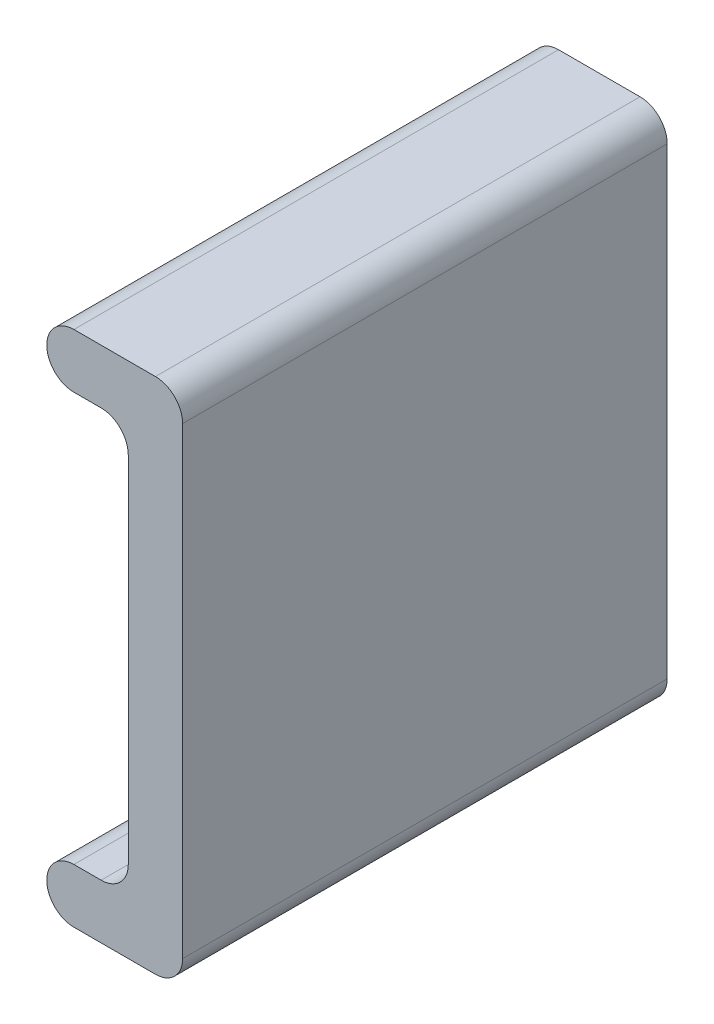
SolidWorks part; units mm, degrees
material "ABS"
ref_plane "X-Y Datum" through (0, 0, 0) normal (0, 0, 1) x (1, 0, 0)
ref_plane "X-Z Datum" through (0, 0, 0) normal (0, 1, 0) x (1, 0, 0)
ref_plane "Y-Z Datum" through (0, 0, 0) normal (1, 0, 0) x (0, 0, -1)
sketch "Sketch1" plane through (0, 0, 0) normal (0, 0, 1) x (1, 0, 0)
  line L1 (0, 0) -> (15, 0)
  line L2 (0, 0) -> (0, 6)
  line L3 (0, 6) -> (9, 6)
  line L4 (15, 0) -> (15, 6.15)
  line L6 (15, 6.15) -> (15, 57.15)
  line L8 (9, 6) -> (9, 51.15)
  line L9 (15, 57.15) -> (0, 57.15)
  line L10 (15, 57.15) -> (15, 53.7541)
  line L11 (9, 51.15) -> (0, 51.15)
  line L12 (0, 57.15) -> (0, 51.15)
  point P12 (0, 54.15)
  dimension "D1" = 15
  dimension "D2" = 57.15
  dimension "D3" = 6
  dimension "D4" = 6
  dimension "D5" = 6
  dimension "D6" = 15
extrude "Boss-Extrude1" add sketch "Sketch1" along normal blind 53.5 contours L9 L12 L11 L8 L3 L2 L1 L4 L6 region at (10.2036, 28.575, 0)
fillet "Fillet4" radius 3 8 edges at (0, 6, 26.75) (9, 6, 26.75) (15, 0, 26.75) (0, 0, 26.75) (15, 57.15, 26.75) (0, 57.15, 26.75) (9, 51.15, 26.75) (0, 51.15, 26.75)
